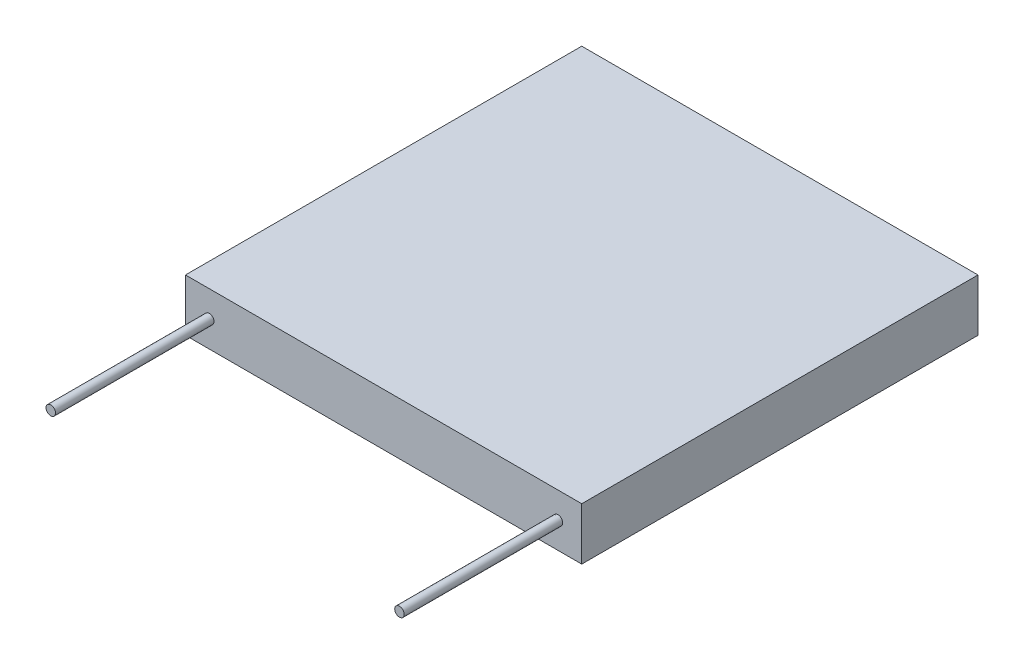
SolidWorks part; units mm, degrees
ref_plane "前视基准面" through (0, 0, 0) normal (0, 0, 1) x (1, 0, 0)
ref_plane "上视基准面" through (0, 0, 0) normal (0, 1, 0) x (1, 0, 0)
ref_plane "右视基准面" through (0, 0, 0) normal (1, 0, 0) x (0, 0, -1)
sketch "草图1" plane through (0, 0, 0) normal (0, 1, 0) x (1, 0, 0)
  line L0 (-59.7364, 0) -> (83.9948, 0) construction
  line L1 (-12.5, 12.5) -> (12.5, 12.5)
  line L2 (-12.5, 12.5) -> (-12.5, -12.5)
  line L3 (-12.5, -12.5) -> (12.5, -12.5)
  line L4 (12.5, 12.5) -> (12.5, -12.5)
  line L5 (0, 52.7621) -> (0, -60.9493) construction
  dimension "D1" = 25
  dimension "D2" = 25
extrude "拉伸1" add sketch "草图1" along normal blind 1.65 and the other way blind 1.65
sketch "草图2" plane through (0, 0, 12.5) normal (0, 0, 1) x (1, 0, 0)
  line L0 (-9.3144, 0) -> (9.8458, 0) construction
  line L1 (-12.5, 1.65) -> (12.5, 1.65) construction
  line L2 (-12.5, -1.65) -> (12.5, -1.65) construction
  line L3 (0, 5.0008) -> (0, -4.2198) construction
  line L4 (-11, 3.3543) -> (-11, -1.6197) construction
  circle A0 centre (-11, 0) radius 0.3
  circle A1 centre (11, 0) radius 0.3
  dimension "D2" = 0.6
  dimension "D1" = 11
extrude "拉伸2" add sketch "草图2" along normal blind 10
